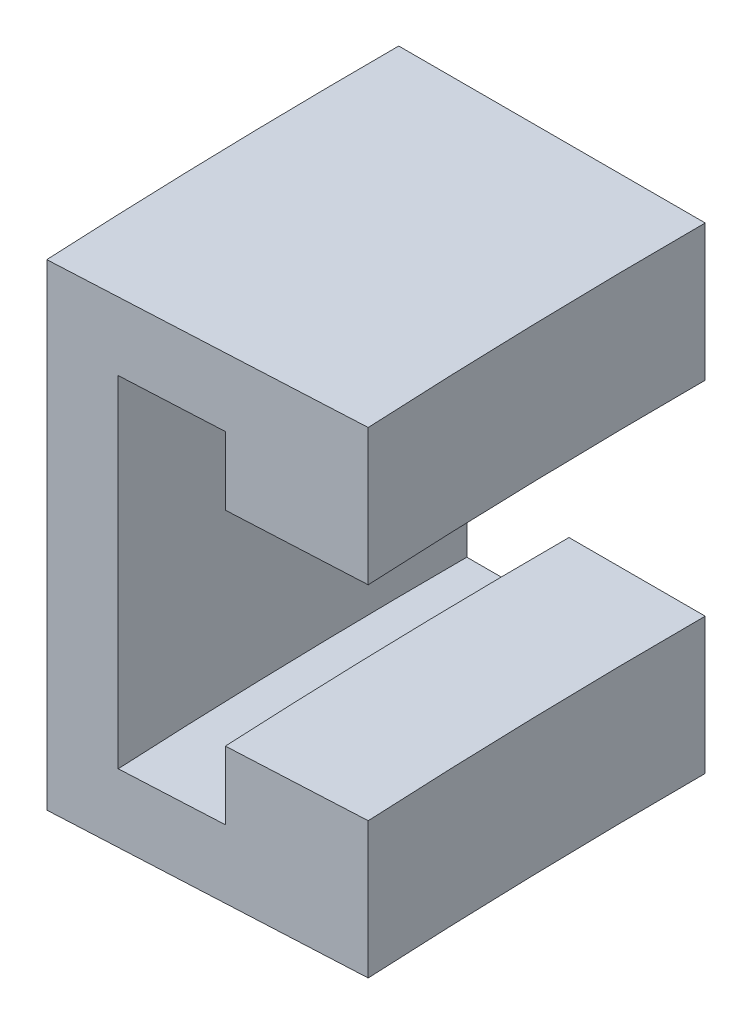
SolidWorks part; units mm, degrees
ref_plane "Front Plane" through (0, 0, 0) normal (0, 0, 1) x (1, 0, 0)
ref_plane "Top Plane" through (0, 0, 0) normal (0, 1, 0) x (1, 0, 0)
ref_plane "Right Plane" through (0, 0, 0) normal (1, 0, 0) x (0, 0, -1)
sketch "Sketch1" plane through (0, 0, 0) normal (0, 0, 1) x (1, 0, 0)
  line L0 (0, 25) -> (0, -25)
  line L1 (0, -25) -> (15, -25)
  line L2 (15, -25) -> (15, -15)
  line L3 (15, -15) -> (35, -15)
  line L4 (35, -15) -> (35, -35)
  line L5 (35, -35) -> (-10, -35)
  line L6 (-10, -35) -> (-10, 35)
  line L12 (0, 0) -> (-10, 0) construction
  line L13 (35, 35) -> (-10, 35)
  line L14 (35, 15) -> (35, 35)
  line L15 (15, 15) -> (35, 15)
  line L16 (15, 25) -> (15, 15)
  line L17 (0, 25) -> (15, 25)
  dimension "D1" = 15
  dimension "D2" = 20
  dimension "D3" = 25
  dimension "D4" = 10
  dimension "D5" = 10
  dimension "D6" = 10
extrude "Boss-Extrude1" [suppressed] add sketch "Sketch1" along normal blind 50
sketch "Sketch3" plane through (0, 0, 0) normal (0, 1, 0) x (1, 0, 0)
  line L0 (0, -50) -> (51.2508, -50) construction
  line L1 (0, 0) -> (50, 0) construction
  arc A0 (50, 0) -> (51.2508, -50) centre (1050, 0) ccw
  dimension "D1" = 15
  dimension "D2" = 2000
  dimension "D3" = 50
sweep "Sweep1" add profiles "Sketch1<2>" path "Sketch3"
sketch "Sketch1<2>" plane through (0, 0, 0) normal (0, 0, 1) x (1, 0, 0) same geometry as "Sketch1"
